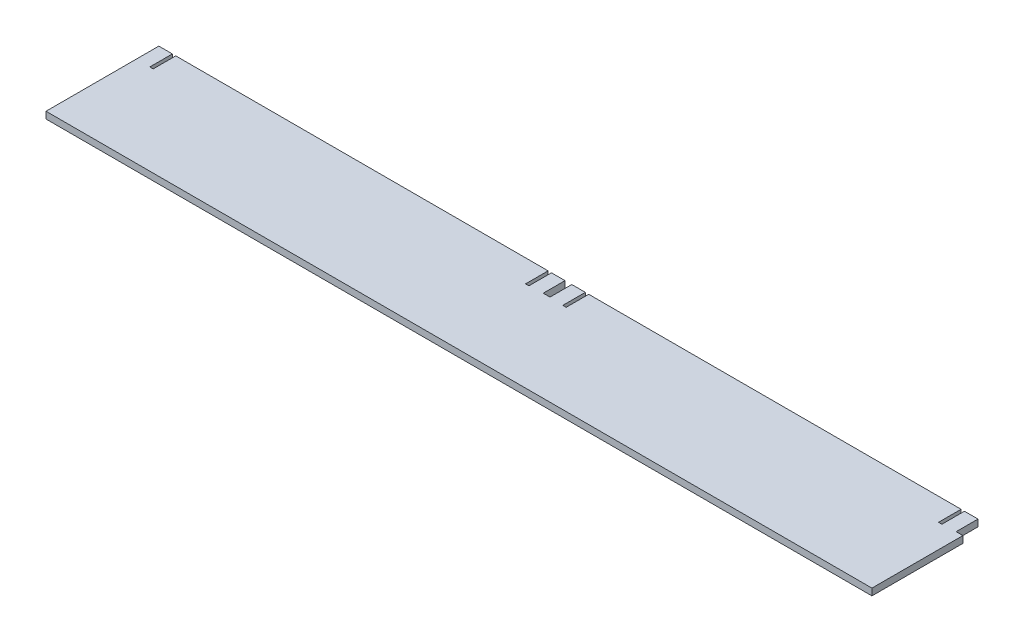
SolidWorks part; units mm, degrees
ref_plane "Front Plane" through (0, 0, 0) normal (0, 0, 1) x (1, 0, 0)
ref_plane "Top Plane" through (0, 0, 0) normal (0, 1, 0) x (1, 0, 0)
ref_plane "Right Plane" through (0, 0, 0) normal (1, 0, 0) x (0, 0, -1)
sketch "Sketch1" plane through (0, 0, 0) normal (0, 1, 0) x (1, 0, 0)
  line L0 (-84, 25) -> (-84, 15)
  line L1 (-90, -25) -> (90, -25)
  line L2 (-90, -25) -> (-90, 25)
  line L3 (-90, 25) -> (-84, 25)
  line L4 (90, -25) -> (90, 25)
  line L5 (-84, 15) -> (-82.5, 15)
  line L6 (-82.5, 15) -> (-82.5, 25)
  line L7 (82.5, 25) -> (82.5, 15)
  line L8 (82.5, 15) -> (84, 15)
  line L9 (84, 15) -> (84, 25)
  line L10 (-82.5, 25) -> (82.5, 25)
  line L11 (84, 25) -> (90, 25)
  point P4 (-90, 0)
  point P5 (0, 25)
  dimension "D1" = 50
  dimension "D2" = 180
  dimension "D3" = 6
  dimension "D4" = 1.5
  dimension "D5" = 10
extrude "Boss-Extrude1" add sketch "Sketch1" along normal mid plane 3
sketch "Sketch2" plane through (0, 0, 0) normal (0, 1, 0) x (1, 0, 0)
  line L0 (90, -25) -> (90, 25) construction
  line L1 (90, 15.3314) -> (93, 15.3314)
  line L2 (90, 15.3314) -> (90, -25)
  line L3 (90, -25) -> (93, -25)
  line L4 (93, 15.3314) -> (93, -25)
  line L5 (-90, -25) -> (90, -25) construction
  dimension "D1" = 3
extrude "Boss-Extrude2" add sketch "Sketch2" along normal mid plane 3
pattern_linear "LPattern2" count 2 spacing 183 along (1, 0, 0) of "Boss-Extrude1", "Boss-Extrude2"
equation "\"mdfWidth\"= 3"
equation "\"cellSide\"= 180"
equation "\"mazeHeight\" = 50"
equation "\"slitHeight\"= 10"
equation "\"slitWidth\" = \"wallThickness\""
equation "\"gripWidth\"= 6"
equation "\"wallThickness\"= 1.5"
equation "\"D1@Sketch1\"= \"mazeHeight\""
equation "\"D2@Sketch1\"= \"cellSide\""
equation "\"D3@Sketch1\"= \"gripWidth\""
equation "\"D4@Sketch1\"= \"wallThickness\""
equation "\"D5@Sketch1\"= \"slitHeight\""
equation "\"D1@Boss-Extrude1\"= \"mdfWidth\""
equation "\"D1@Sketch2\"= \"mdfWidth\""
equation "\"D1@Boss-Extrude2\"= \"mdfWidth\""
equation "\"D1@LPattern1\"= 2"
equation "\"D3@LPattern1\"= \"cellSide\" + \"mdfWidth\""
equation "\"nbUnits\"= 2"
equation "\"D1@LPattern2\"= \"nbUnits\""
